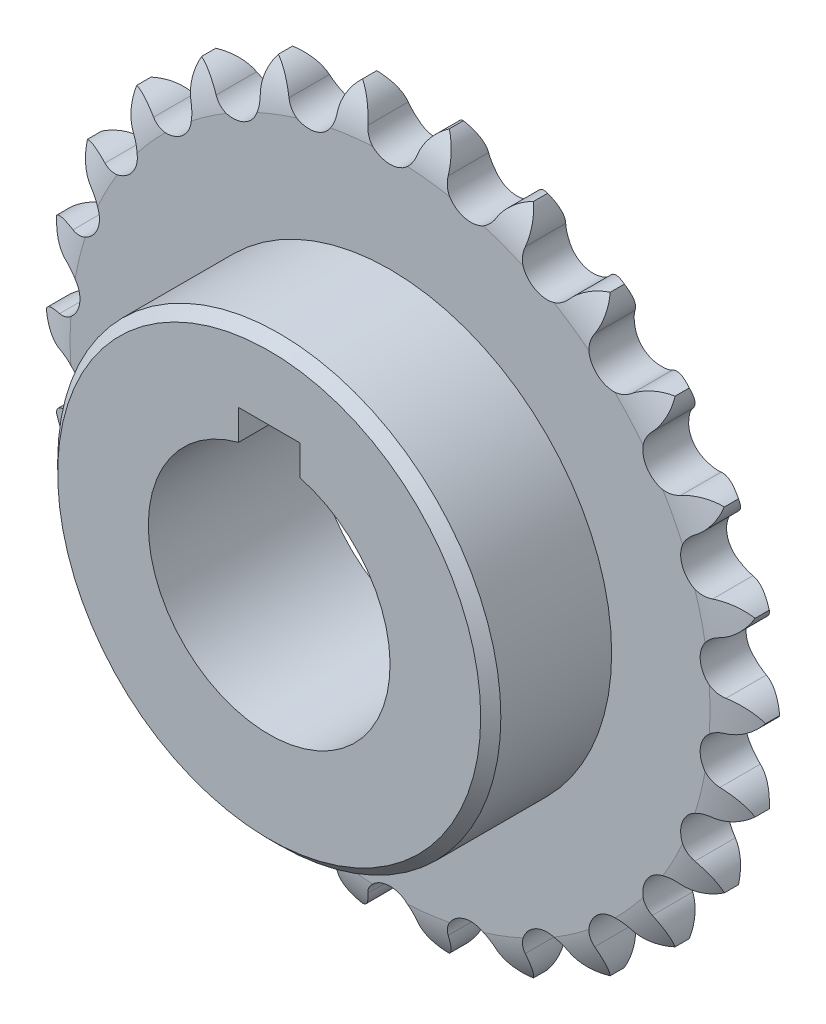
SolidWorks part; units mm, degrees
ref_plane "Front Plane" through (0, 0, 0) normal (0, 0, 1) x (1, 0, 0)
ref_plane "Top Plane" through (0, 0, 0) normal (0, 1, 0) x (1, 0, 0)
ref_plane "Right Plane" through (0, 0, 0) normal (1, 0, 0) x (0, 0, -1)
sketch "Sketch1" plane through (0, 0, 0) normal (0, 0, 1) x (1, 0, 0)
  line L0 (0, 0) -> (0, 56.7055) construction
  line L1 (0, 0) -> (9.6217, 51.1475) construction
  line L2 (0, 0) -> (9.6217, 51.1475) construction
  line L3 (0, 0) -> (21.5825, 47.3586) construction
  circle A0 centre (0, 0) radius 19.05
  circle A1 centre (0, 0) radius 49.2633 construction
  circle A2 centre (0, 0) radius 52.0446 construction
  circle A3 centre (0, 0) radius 53.2892 construction
  circle A4 centre (0, 0) radius 56.7055 construction
  arc A5 (3.9297, 52.4145) -> (-3.9297, 52.4145) centre (0, 53.2892) cw
  arc A6 (3.9297, 52.4145) -> (6.8687, 56.288) centre (9.6217, 51.1475) cw
  arc A7 (-3.9297, 52.4145) -> (-6.8687, 56.288) centre (-9.6217, 51.1475) ccw
  arc A8 (8.7281, 51.8318) -> (6.8015, 56.2961) centre (2.8983, 51.9638) ccw
  arc A9 (16.3591, 49.951) -> (8.7281, 51.8318) centre (12.7529, 51.7407) cw
  arc A10 (16.3591, 49.951) -> (20.1397, 53.0086) centre (21.5825, 47.3586) cw
  arc A11 (20.8786, 48.2369) -> (20.0764, 53.0326) centre (15.2499, 49.7602) ccw
  arc A12 (27.8378, 44.5845) -> (20.8786, 48.2369) centre (24.7647, 47.1852) cw
  arc A13 (27.8378, 44.5845) -> (32.2402, 46.6485) centre (32.289, 40.8174) cw
  arc A14 (31.8158, 41.8387) -> (32.1845, 46.6869) centre (26.7151, 44.6648) ccw
  arc A15 (37.6987, 36.6269) -> (31.8158, 41.8387) centre (35.3373, 39.8875) cw
  arc A16 (37.6987, 36.6269) -> (42.4671, 37.5774) centre (41.119, 31.9041) cw
  arc A17 (40.9039, 33.0089) -> (42.4222, 37.628) centre (36.6278, 36.9736) ccw
  arc A18 (45.3686, 26.5407) -> (40.9039, 33.0089) centre (43.8562, 30.2717) cw
  arc A19 (45.3686, 26.5407) -> (50.2259, 26.3224) centre (47.5593, 21.1366) cw
  arc A20 (47.6149, 22.2608) -> (50.1945, 26.3823) centre (44.4118, 27.1336) ccw
  arc A21 (50.4019, 14.9121) -> (47.6149, 22.2608) centre (49.8263, 18.8966) cw
  arc A22 (50.4019, 14.9121) -> (55.0658, 13.5376) centre (51.2356, 9.1407) cw
  arc A23 (51.5586, 10.2189) -> (55.0496, 13.6034) centre (49.6148, 15.7167) ccw
  arc A24 (52.506, 2.4168) -> (51.5586, 10.2189) centre (52.9007, 6.4233) cw
  arc A25 (52.506, 2.4168) -> (56.7055, -0.0338) centre (51.9343, -3.3864) cw
  arc A26 (52.506, -2.4168) -> (56.7055, 0.0338) centre (51.9343, 3.3864) ccw
  arc A27 (51.5586, -10.2189) -> (52.506, -2.4168) centre (52.9007, -6.4233) cw
  arc A28 (51.5586, -10.2189) -> (55.0496, -13.6034) centre (49.6148, -15.7167) cw
  arc A29 (50.4019, -14.9121) -> (55.0658, -13.5376) centre (51.2356, -9.1407) ccw
  arc A30 (47.6149, -22.2608) -> (50.4019, -14.9121) centre (49.8263, -18.8966) cw
  arc A31 (47.6149, -22.2608) -> (50.1945, -26.3823) centre (44.4118, -27.1336) cw
  arc A32 (45.3686, -26.5407) -> (50.2259, -26.3224) centre (47.5593, -21.1366) ccw
  arc A33 (40.9039, -33.0089) -> (45.3686, -26.5407) centre (43.8562, -30.2717) cw
  arc A34 (40.9039, -33.0089) -> (42.4222, -37.628) centre (36.6278, -36.9736) cw
  arc A35 (37.6987, -36.6269) -> (42.4671, -37.5774) centre (41.119, -31.9041) ccw
  arc A36 (31.8158, -41.8387) -> (37.6987, -36.6269) centre (35.3373, -39.8875) cw
  arc A37 (31.8158, -41.8387) -> (32.1845, -46.6869) centre (26.7151, -44.6648) cw
  arc A38 (27.8378, -44.5845) -> (32.2402, -46.6485) centre (32.289, -40.8174) ccw
  arc A39 (20.8786, -48.2369) -> (27.8378, -44.5845) centre (24.7647, -47.1852) cw
  arc A40 (20.8786, -48.2369) -> (20.0764, -53.0326) centre (15.2499, -49.7602) cw
  arc A41 (16.3591, -49.951) -> (20.1397, -53.0086) centre (21.5825, -47.3586) ccw
  arc A42 (8.7281, -51.8318) -> (16.3591, -49.951) centre (12.7529, -51.7407) cw
  arc A43 (8.7281, -51.8318) -> (6.8015, -56.2961) centre (2.8983, -51.9638) cw
  arc A44 (3.9297, -52.4145) -> (6.8687, -56.288) centre (9.6217, -51.1475) ccw
  arc A45 (-3.9297, -52.4145) -> (3.9297, -52.4145) centre (0, -53.2892) cw
  arc A46 (-3.9297, -52.4145) -> (-6.8687, -56.288) centre (-9.6217, -51.1475) cw
  arc A47 (-8.7281, -51.8318) -> (-6.8015, -56.2961) centre (-2.8983, -51.9638) ccw
  arc A48 (-16.3591, -49.951) -> (-8.7281, -51.8318) centre (-12.7529, -51.7407) cw
  arc A49 (-16.3591, -49.951) -> (-20.1397, -53.0086) centre (-21.5825, -47.3586) cw
  arc A50 (-20.8786, -48.2369) -> (-20.0764, -53.0326) centre (-15.2499, -49.7602) ccw
  arc A51 (-27.8378, -44.5845) -> (-20.8786, -48.2369) centre (-24.7647, -47.1852) cw
  arc A52 (-27.8378, -44.5845) -> (-32.2402, -46.6485) centre (-32.289, -40.8174) cw
  arc A53 (-31.8158, -41.8387) -> (-32.1845, -46.6869) centre (-26.7151, -44.6648) ccw
  arc A54 (-37.6987, -36.6269) -> (-31.8158, -41.8387) centre (-35.3373, -39.8875) cw
  arc A55 (-37.6987, -36.6269) -> (-42.4671, -37.5774) centre (-41.119, -31.9041) cw
  arc A56 (-40.9039, -33.0089) -> (-42.4222, -37.628) centre (-36.6278, -36.9736) ccw
  arc A57 (-45.3686, -26.5407) -> (-40.9039, -33.0089) centre (-43.8562, -30.2717) cw
  arc A58 (-45.3686, -26.5407) -> (-50.2259, -26.3224) centre (-47.5593, -21.1366) cw
  arc A59 (-47.6149, -22.2608) -> (-50.1945, -26.3823) centre (-44.4118, -27.1336) ccw
  arc A60 (-50.4019, -14.9121) -> (-47.6149, -22.2608) centre (-49.8263, -18.8966) cw
  arc A61 (-50.4019, -14.9121) -> (-55.0658, -13.5376) centre (-51.2356, -9.1407) cw
  arc A62 (-51.5586, -10.2189) -> (-55.0496, -13.6034) centre (-49.6148, -15.7167) ccw
  arc A63 (-52.506, -2.4168) -> (-51.5586, -10.2189) centre (-52.9007, -6.4233) cw
  arc A64 (-52.506, -2.4168) -> (-56.7055, 0.0338) centre (-51.9343, 3.3864) cw
  arc A65 (-52.506, 2.4168) -> (-56.7055, -0.0338) centre (-51.9343, -3.3864) ccw
  arc A66 (-51.5586, 10.2189) -> (-52.506, 2.4168) centre (-52.9007, 6.4233) cw
  arc A67 (-51.5586, 10.2189) -> (-55.0496, 13.6034) centre (-49.6148, 15.7167) cw
  arc A68 (-50.4019, 14.9121) -> (-55.0658, 13.5376) centre (-51.2356, 9.1407) ccw
  arc A69 (-47.6149, 22.2608) -> (-50.4019, 14.9121) centre (-49.8263, 18.8966) cw
  arc A70 (-47.6149, 22.2608) -> (-50.1945, 26.3823) centre (-44.4118, 27.1336) cw
  arc A71 (-45.3686, 26.5407) -> (-50.2259, 26.3224) centre (-47.5593, 21.1366) ccw
  arc A72 (-40.9039, 33.0089) -> (-45.3686, 26.5407) centre (-43.8562, 30.2717) cw
  arc A73 (-40.9039, 33.0089) -> (-42.4222, 37.628) centre (-36.6278, 36.9736) cw
  arc A74 (-37.6987, 36.6269) -> (-42.4671, 37.5774) centre (-41.119, 31.9041) ccw
  arc A75 (-31.8158, 41.8387) -> (-37.6987, 36.6269) centre (-35.3373, 39.8875) cw
  arc A76 (-31.8158, 41.8387) -> (-32.1845, 46.6869) centre (-26.7151, 44.6648) cw
  arc A77 (-27.8378, 44.5845) -> (-32.2402, 46.6485) centre (-32.289, 40.8174) ccw
  arc A78 (-20.8786, 48.2369) -> (-27.8378, 44.5845) centre (-24.7647, 47.1852) cw
  arc A79 (-20.8786, 48.2369) -> (-20.0764, 53.0326) centre (-15.2499, 49.7602) cw
  arc A80 (-16.3591, 49.951) -> (-20.1397, 53.0086) centre (-21.5825, 47.3586) ccw
  arc A81 (-8.7281, 51.8318) -> (-16.3591, 49.951) centre (-12.7529, 51.7407) cw
  arc A82 (-8.7281, 51.8318) -> (-6.8015, 56.2961) centre (-2.8983, 51.9638) cw
  dimension "D1" = 113.411
  dimension "D2" = 106.5784
  dimension "D3" = 104.0892
  dimension "D4" = 98.5266
  dimension "D5" = 5.8313
  dimension "D6" = 38.1
  dimension "D8" = 13.846
  dimension "D7" = 26
extrude "Boss-Extrude1" add sketch "Sketch1" along normal mid plane 7.231 contours A82 A81 A80 A79 A78 A77 A76 A75 A74 A73 A72 A71 A70 A69 A68 A67 A66 A65 A64 A63 A62 A61 A60 A59 A58 A57 A56 A55 A54 A53 A52 A51 A50 A49 A48 A47 A46 A45 A44 A43 A42 A41 A40 A39 A38 A37 A36 A35 A34 A33 A32 region at (6.2397, 53.6946, 0)
sketch "Sketch2" plane through (0, 0, 0) normal (1, 0, 0) x (0, 0, -1)
  line L1 (-3.6155, 19.05) -> (-22.6655, 19.05)
  line L2 (-3.6155, 19.05) -> (-3.6155, 34.925)
  line L3 (-3.6155, 34.925) -> (-22.6655, 34.925)
  line L4 (-22.6655, 19.05) -> (-22.6655, 34.925)
  line L5 (0, 0) -> (-78.0193, 0) construction
  line L6 (-3.6155, 37.5868) -> (-3.6155, 33.0089) construction
  dimension "D1" = 38.1
  dimension "D2" = 69.85
  dimension "D3" = 19.05
revolve "Revolve1" add sketch "Sketch2" angle 360 about L5
sketch "Sketch3" plane through (0, 0, 22.6655) normal (0, 0, 1) x (1, 0, 0)
  line L0 (0, 0) -> (0, 23.2292) construction
  line L2 (-4.825, 18.4288) -> (4.825, 18.4288)
  line L3 (-4.825, 18.4288) -> (-4.825, 23.1888)
  line L4 (-4.825, 23.1888) -> (4.825, 23.1888)
  line L5 (4.825, 18.4288) -> (4.825, 23.1888)
  circle A1 centre (0, 0) radius 19.05 construction
  dimension "D1" = 9.65
  dimension "D2" = 4.76
extrude "Cut-Extrude1" cut sketch "Sketch3" against normal through all
sketch "Sketch4" plane through (0, 0, 0) normal (1, 0, 0) x (0, 0, -1)
  line L0 (0, 0) -> (-64.3119, 0) construction
  line L1 (-3.6155, 50.42) -> (-12.3309, 50.42)
  line L2 (-12.3309, 50.42) -> (-12.3309, 56.89)
  line L3 (-12.3309, 56.89) -> (-0.954, 56.89)
  line L4 (0, 35.4921) -> (0, 64.3319) construction
  line L5 (-3.6155, 52.9981) -> (-3.6155, 48.2369) construction
  arc A0 (-0.954, 56.89) -> (-3.6155, 50.42) centre (9.006, 49.0105) ccw
  dimension "D1" = 50.42
  dimension "D3" = 12.7
  dimension "D2" = 56.89
revolve "Cut-Revolve1" cut sketch "Sketch4" angle 360 about L0
mirror "Mirror1" about plane through (0, 0, 0) normal (0, 0, 1) of "Cut-Revolve1"
chamfer "Chamfer2" distance 1.5875 angle 45 1 edges at (-34.925, 0, 22.6655)
ref_axis "Axis1" through (0, 0, 22.6655) along (0, 0, -1)
sketch "草图1" plane through (0, 0, -3.6155) normal (0, 0, -1) x (-1, 0, 0)
  circle A0 centre (0, 0) radius 53.848
sketch "草图2" plane through (0, 0, -3.6155) normal (0, 0, -1) x (-1, 0, 0)
  circle A0 centre (0, 0) radius 53.848
